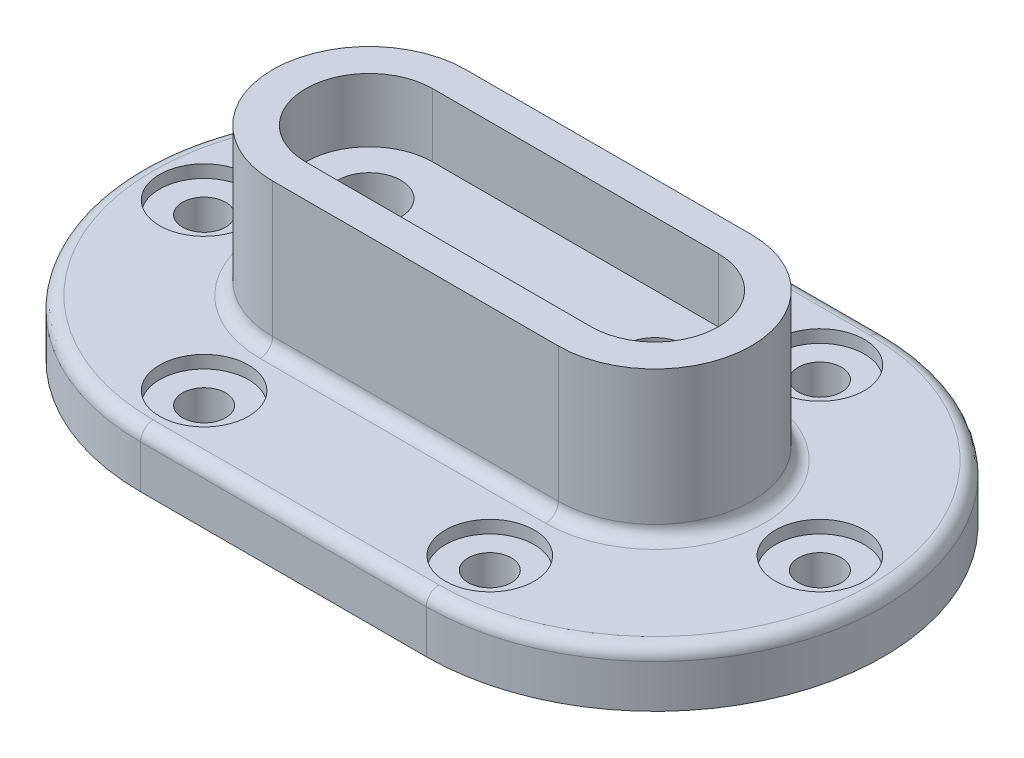
SolidWorks part; units mm, degrees
ref_plane "Front Plane" through (0, 0, 0) normal (0, 0, 1) x (1, 0, 0)
ref_plane "Top Plane" through (0, 0, 0) normal (0, 1, 0) x (1, 0, 0)
ref_plane "Right Plane" through (0, 0, 0) normal (1, 0, 0) x (0, 0, -1)
sketch "Sketch1" plane through (0, 0, 0) normal (0, 1, 0) x (1, 0, 0)
  line L0 (-11.25, 0) -> (11.25, 0) construction
  line L1 (-11.25, 18) -> (11.25, 18)
  line L2 (-11.25, -18) -> (11.25, -18)
  arc A0 (-11.25, 18) -> (-11.25, -18) centre (-11.25, 0) ccw
  arc A1 (11.25, -18) -> (11.25, 18) centre (11.25, 0) ccw
  point P2 (0, 0)
  dimension "D2" = 18
  dimension "D1" = 22.5
extrude "Boss-Extrude1" add sketch "Sketch1" along normal blind 4.4
sketch "Sketch2" plane through (0, 4.4, 0) normal (0, 1, 0) x (1, 0, 0)
  line L0 (-11.25, 0) -> (11.25, 0) construction
  line L1 (-11.25, 13) -> (11.25, 13) construction
  line L2 (-11.25, -13) -> (11.25, -13) construction
  arc A0 (-11.25, 13) -> (-11.25, -13) centre (-11.25, 0) ccw construction
  arc A1 (11.25, -13) -> (11.25, 13) centre (11.25, 0) ccw construction
  circle A2 centre (-24.25, 0) radius 3.5
  circle A3 centre (-11.25, 13) radius 3.5
  circle A4 centre (11.25, 13) radius 3.5
  circle A5 centre (24.25, 0) radius 3.5
  circle A6 centre (11.25, -13) radius 3.5
  circle A7 centre (-11.25, -13) radius 3.5
  circle A8 centre (-11.25, 13) radius 1.7
  circle A9 centre (-24.25, 0) radius 1.7
  circle A10 centre (-11.25, -13) radius 1.7
  circle A11 centre (11.25, -13) radius 1.7
  circle A12 centre (24.25, 0) radius 1.7
  circle A13 centre (11.25, 13) radius 1.7
  point P2 (0, 0)
  dimension "D2" = 13
  dimension "D3" = 7
  dimension "D4" = 3.4
  dimension "D1" = 22.5
extrude "Cut-Extrude1" cut sketch "Sketch2" against normal blind 1 contours A2 | A3 | A4 | A5 | A6 | A7
extrude "Cut-Extrude2" cut sketch "Sketch2<3>" against normal through all contours A9 | A8 | A13 | A12 | A11 | A10
sketch "Sketch2<3>" plane through (0, 4.4, 0) normal (0, 1, 0) x (1, 0, 0) same geometry as "Sketch2"
sketch "Sketch3" plane through (0, 4.4, 0) normal (0, 1, 0) x (1, 0, 0)
  line L0 (-17.2337, 0) -> (11.25, 0) construction
  line L1 (-11.25, 0) -> (11.25, 0) construction
  line L2 (-11.25, 7.6) -> (11.25, 7.6)
  line L3 (-11.25, -7.6) -> (11.25, -7.6)
  arc A0 (-11.25, 7.6) -> (-11.25, -7.6) centre (-11.25, 0) ccw
  arc A1 (11.25, -7.6) -> (11.25, 7.6) centre (11.25, 0) ccw
  point P4 (0, 0)
  dimension "D2" = 7.6
  dimension "D1" = 22.5
extrude "Boss-Extrude2" add sketch "Sketch3" along normal blind 11.6
fillet "Fillet1" radius 1 8 edges at (-18.85, 4.4, 0) (0, 4.4, -7.6) (18.85, 4.4, 0) (-29.25, 4.4, 0) (0, 4.4, -18) (29.25, 4.4, 0) (0, 4.4, 7.6) (0, 4.4, 18)
sketch "Sketch4" plane through (0, 16, 0) normal (0, 1, 0) x (1, 0, 0)
  line L0 (-11.25, 0) -> (11.25, 0) construction
  line L1 (-11.25, 5) -> (11.25, 5)
  line L2 (-11.25, -5) -> (11.25, -5)
  arc A0 (-11.25, 5) -> (-11.25, -5) centre (-11.25, 0) ccw
  arc A1 (11.25, -5) -> (11.25, 5) centre (11.25, 0) ccw
  point P2 (0, 0)
  dimension "D2" = 5
  dimension "D1" = 22.5
extrude "Cut-Extrude3" cut sketch "Sketch4" against normal blind 5
sketch "Sketch5" plane through (0, 11, 0) normal (0, 1, 0) x (1, 0, 0)
  circle A0 centre (-11.25, 0) radius 2.5
  circle A1 centre (11.25, 0) radius 2.5
  dimension "D1" = 5
extrude "Cut-Extrude4" cut sketch "Sketch5" against normal up to surface (11 mm away) up to face at (-11.25, 0, -11.3)
